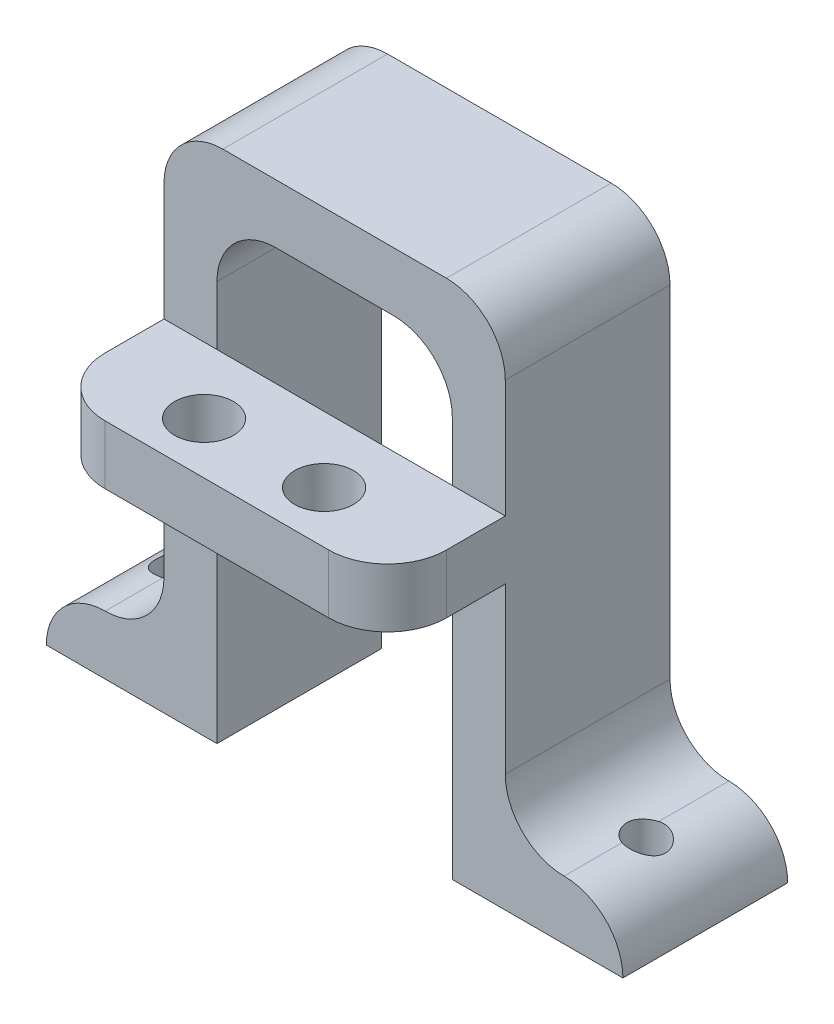
SolidWorks part; units mm, degrees
ref_plane "Front Plane" through (0, 0, 0) normal (0, 0, 1) x (1, 0, 0)
ref_plane "Top Plane" through (0, 0, 0) normal (0, 1, 0) x (1, 0, 0)
ref_plane "Right Plane" through (0, 0, 0) normal (1, 0, 0) x (0, 0, -1)
sketch "Sketch1" plane through (0, 0, 0) normal (0, 0, 1) x (1, 0, 0)
  line L0 (-24.5, 0) -> (-24.5, 5)
  line L1 (7.7, 0) -> (-7.7, 0) construction
  line L2 (-24.5, 5) -> (-14.5, 5)
  line L3 (-14.5, 5) -> (-14.5, 44)
  line L4 (-14.5, 44) -> (14.5, 44)
  line L5 (-24.5, 0) -> (-10, 0)
  line L6 (-10, 0) -> (-10, 39)
  line L7 (-10, 39) -> (10, 39)
  line L8 (0, -16.5) -> (0, 16.5) construction
  line L9 (24.5, 0) -> (10, 0)
  line L10 (24.5, 0) -> (24.5, 5)
  line L11 (24.5, 5) -> (14.5, 5)
  line L12 (10, 0) -> (10, 39)
  line L13 (14.5, 5) -> (14.5, 44)
  point P7 (0, 39)
  point P19 (0, 44)
  dimension "D1" = 20
  dimension "D2" = 5
  dimension "D4" = 5
  dimension "D6" = 39
extrude "Boss-Extrude1" add sketch "Sketch1" along normal blind 14
fillet "Fillet1" radius 5 6 edges at (-14.5, 44, 7) (14.5, 44, 7) (24.5, 5, 7) (-24.5, 5, 7) (14.5, 5, 7) (-14.5, 5, 7)
fillet "Fillet2" radius 5 2 edges at (10, 39, 7) (-10, 39, 7)
sketch "Sketch2" plane through (0, 0, 0) normal (0, 1, 0) x (1, 0, 0)
  line L0 (0, -16.5) -> (0, 16.5) construction
  circle A0 centre (-20, -7.5233) radius 1.636
  circle A1 centre (20, -7.5233) radius 1.636
  dimension "D1" = 40
extrude "Cut-Extrude3" cut sketch "Sketch2" against normal blind 10 and the other way blind 10 contours A0 | A1
sketch "Sketch4" plane through (0, 0, 14) normal (0, 0, 1) x (1, 0, 0)
  line L0 (-14.5, 39) -> (-14.5, 10) construction
  line L1 (9.5, 44) -> (-9.5, 44)
  line L2 (9.5, 44) -> (9.5, 39)
  line L3 (9.5, 39) -> (-9.5, 39)
  line L4 (-9.5, 44) -> (-9.5, 39)
  line L5 (-14.5, 29) -> (14.5, 29)
  line L6 (-14.5, 29) -> (-14.5, 24)
  line L7 (-14.5, 24) -> (14.5, 24)
  line L8 (14.5, 29) -> (14.5, 24)
  line L9 (14.5, 10) -> (14.5, 39) construction
  dimension "D1" = 15
  dimension "D2" = 5
extrude "Boss-Extrude2" add sketch "Sketch4" along normal blind 10 contours L6 L5 L8 L7
sketch "Sketch5" plane through (0, 44, 0) normal (0, 1, 0) x (1, 0, 0)
  circle A0 centre (4.7058, -19.6015) radius 2.5
  circle A1 centre (-5.4774, -19.6181) radius 2.5
  dimension "D1" = 5
  dimension "D2" = 5
extrude "Cut-Extrude4" cut sketch "Sketch5" against normal blind 30
fillet "Fillet3" radius 5 2 edges at (-14.5, 26.5, 24) (14.5, 26.5, 24)
move or copy body "Body-Move/Copy1" [suppressed] bodies to move or copy 109
